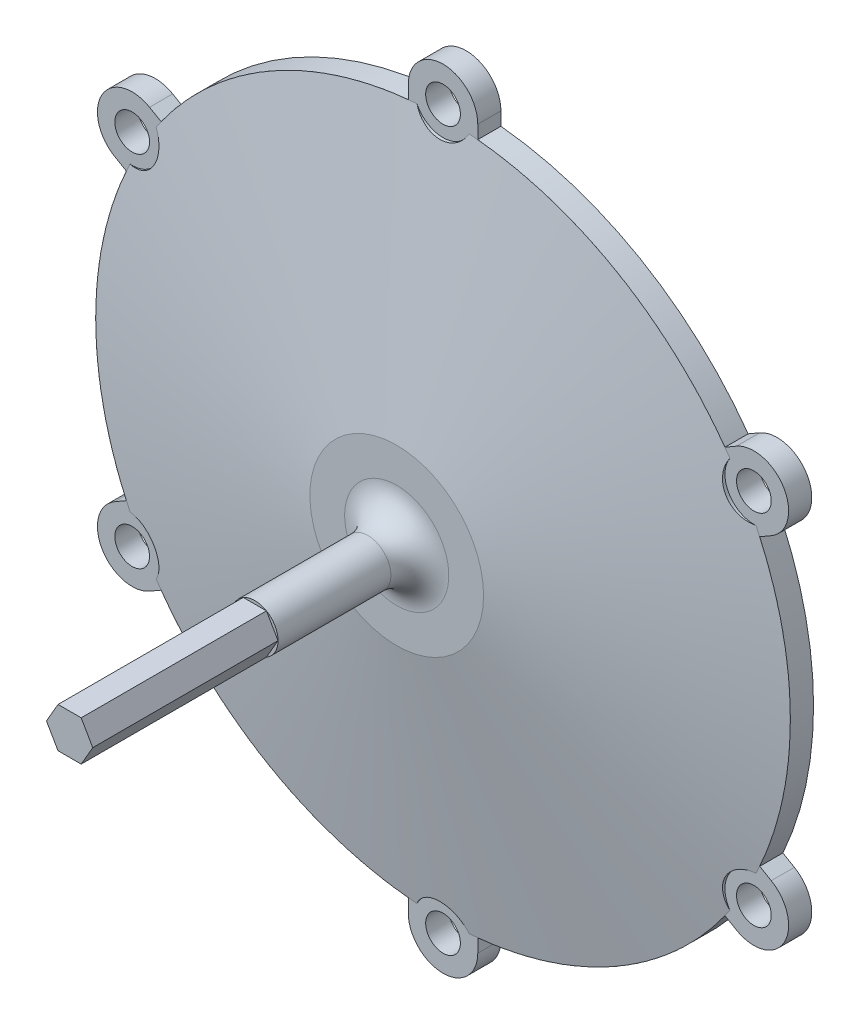
SolidWorks part; units mm, degrees
other "Markup1"
sketch "Sketch15" plane through (-60, 68, 48) normal (-0.9801, 0.1341, 0.1467) x (0.1373, -0.0767, 0.9876)
material "PETG"
ref_plane "Front Plane" through (0, 0, 0) normal (0, 0, 1) x (1, 0, 0)
ref_plane "Top Plane" through (0, 0, 0) normal (0, 1, 0) x (1, 0, 0)
ref_plane "Right Plane" through (0, 0, 0) normal (1, 0, 0) x (0, 0, -1)
sketch "Sketch1" plane through (0, 0, 0) normal (0, 0, 1) x (1, 0, 0)
  line L0 (-6, 62) -> (-6, 59.6992)
  line L1 (6, 62) -> (6, 59.6992)
  line L2 (50.6936, 36.1962) -> (48.7011, 35.0458)
  line L3 (56.6936, 25.8038) -> (54.7011, 24.6535)
  line L4 (56.6936, -25.8038) -> (54.7011, -24.6535)
  line L5 (50.6936, -36.1962) -> (48.7011, -35.0458)
  line L6 (6, -62) -> (6, -59.6992)
  line L7 (-6, -62) -> (-6, -59.6992)
  line L8 (-50.6936, -36.1962) -> (-48.7011, -35.0458)
  line L9 (-56.6936, -25.8038) -> (-54.7011, -24.6535)
  line L10 (-56.6936, 25.8038) -> (-54.7011, 24.6535)
  line L11 (-50.6936, 36.1962) -> (-48.7011, 35.0458)
  line L12 (0, 0) -> (6, 59.6992) construction
  circle A0 centre (0, 0) radius 57
  circle A1 centre (0, 0) radius 60
  arc A2 (6, 62) -> (-6, 62) centre (0, 62) ccw
  arc A3 (56.6936, 25.8038) -> (50.6936, 36.1962) centre (53.6936, 31) ccw
  arc A4 (50.6936, -36.1962) -> (56.6936, -25.8038) centre (53.6936, -31) ccw
  arc A5 (-6, -62) -> (6, -62) centre (0, -62) ccw
  arc A6 (-56.6936, -25.8038) -> (-50.6936, -36.1962) centre (-53.6936, -31) ccw
  arc A7 (-50.6936, 36.1962) -> (-56.6936, 25.8038) centre (-53.6936, 31) ccw
  dimension "D1" = 120
  dimension "D2" = 3
  dimension "D3" = 6
  dimension "D4" = 62
  dimension "D5" = 6
extrude "Boss-Extrude1" add sketch "Sketch1" along normal blind 4 contours L11 A7 L10 A1 | L1 A2 L0 A1 | L3 A3 L2 A1 | L5 A4 L4 A1 | L7 A5 L6 A1 | L9 A6 L8 A1 | A0 A1 region at (0, 63.4372, 0) region at (0, 58.3029, 0) region at (-54.9382, 31.7186, 0) region at (54.9382, 31.7186, 0) region at (-54.9382, -31.7186, 0) region at (54.9382, -31.7186, 0) region at (0, -63.4372, 0)
sketch "Sketch3" plane through (0, 0, 0) normal (0, 1, 0) x (1, 0, 0)
  line L0 (0, -4) -> (60, -4)
  line L1 (-6, -4) -> (6, -4) construction
  line L2 (60, -4) -> (15, -12)
  line L3 (15, -12) -> (0, -12)
  line L4 (0, -12) -> (0, -4)
  line L5 (48.7011, 0) -> (6, 0) construction
  line L6 (48.7011, 0) -> (6, 0) construction
  line L7 (0, -4) -> (60, -4)
  line L8 (0, -4) -> (0, -0.5)
  line L9 (0, -0.5) -> (57, -0.5)
  line L13 (57, -0.5) -> (57, -4)
  line L15 (-57, -4) -> (57, -4) construction
  dimension "D1" = 12
  dimension "D2" = 15
  dimension "D3" = 0.5
  dimension "D4" = 3
revolve "Revolve1" add sketch "Sketch3" angle 360 about L4 region at (28.5, 0, 2.25) region at (21, 0, 7.2)
sketch "Sketch4" plane through (0, 0, 0.5) normal (0, 0, 1) x (1, 0, 0)
  circle A0 centre (0, 0) radius 14
  dimension "D1" = 28
extrude "Cut-Extrude1" cut sketch "Sketch4" along normal blind 7 contours A0
sketch "Sketch9" plane through (0, 0, 7.5) normal (0, 0, -1) x (-1, 0, 0)
  circle A0 centre (0, 0) radius 11.5
  dimension "D1" = 23
extrude "Cut-Extrude4" cut sketch "Sketch9" against normal blind 0.5
sketch "Sketch10" plane through (0, 0, 12) normal (0, 0, 1) x (1, 0, 0)
  circle A0 centre (0, 0) radius 4
  dimension "D1" = 8
extrude "Boss-Extrude2" add sketch "Sketch10" along normal blind 56.5
fillet "Fillet1" radius 5 1 edges at (4, 0, 12)
sketch "Sketch7" plane through (0, 0, 4) normal (0, 0, 1) x (1, 0, 0)
  circle A0 centre (0, 62) radius 3
  arc A1 (6, 62) -> (-6, 62) centre (0, 62) ccw construction
  dimension "D1" = 6
extrude "Cut-Extrude2" cut sketch "Sketch7" against normal through all
sketch "Sketch8" plane through (0, 0, 4) normal (0, 0, 1) x (1, 0, 0)
  circle A0 centre (0, 62) radius 5
  dimension "D1" = 10
extrude "Cut-Extrude3" cut sketch "Sketch8" along normal through all
pattern_circular "CirPattern6" count 6 over 360 about axis through (0, 0, 4) along (0, 0, 1) of "Cut-Extrude2", "Cut-Extrude3"
sketch "Sketch11" plane through (0, 0, 68.5) normal (0, 0, 1) x (1, 0, 0)
  line L5 (2, 3.4641) -> (-2, 3.4641)
  line L6 (-2, 3.4641) -> (-4, 0)
  line L7 (-4, 0) -> (-2, -3.4641)
  line L8 (-2, -3.4641) -> (2, -3.4641)
  line L9 (2, -3.4641) -> (4, 0)
  line L10 (4, 0) -> (2, 3.4641)
  circle A1 centre (0, 0) radius 3.4641 construction
  circle A2 centre (0, 0) radius 4 construction
  circle A3 centre (0, 0) radius 4
  circle M5 centre (0, 0) radius 4
extrude "Cut-Extrude5" cut sketch "Sketch11" against normal blind 32 contours L6 M5 | L5 M5 | L10 M5 | L9 M5 | L8 M5 | L7 M5 region at (3.1867, 1.8399, 68.5) region at (0, 3.6797, 68.5) region at (-3.1867, 1.8399, 68.5) region at (3.1867, -1.8399, 68.5) region at (-3.1867, -1.8399, 68.5) region at (0, -3.6797, 68.5)
